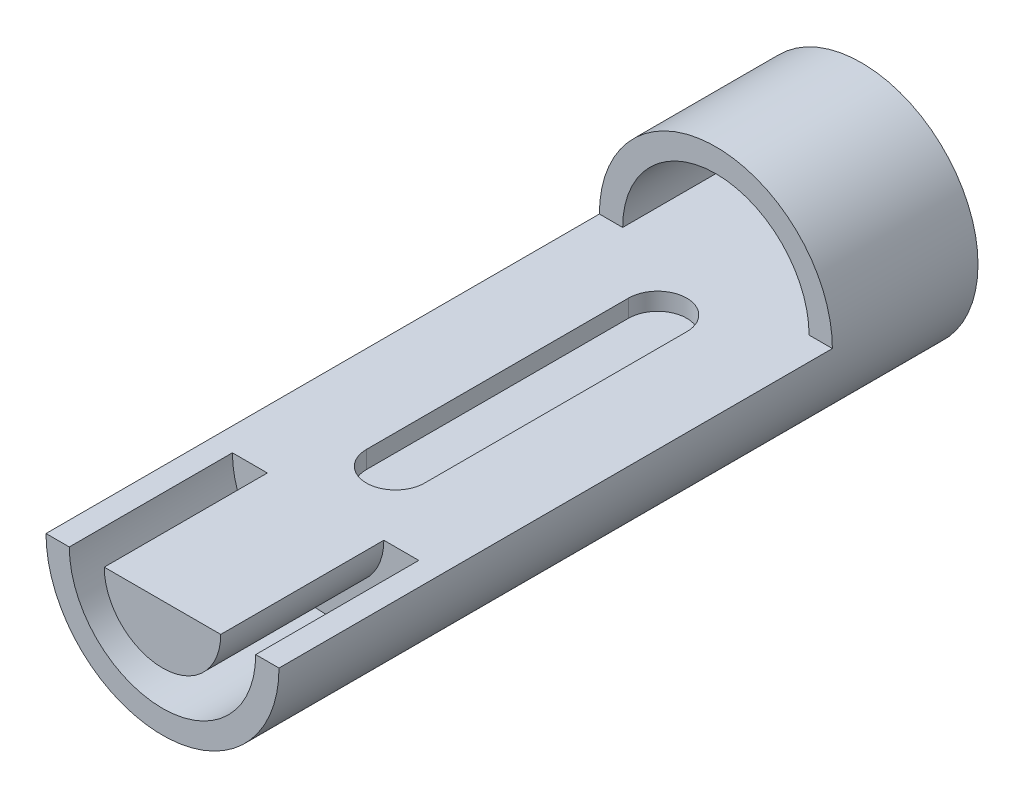
SolidWorks part; units mm, degrees
material "Copper"
ref_plane "Front Plane" through (0, 0, 0) normal (0, 0, 1) x (1, 0, 0)
ref_plane "Top Plane" through (0, 0, 0) normal (0, 1, 0) x (1, 0, 0)
ref_plane "Right Plane" through (0, 0, 0) normal (1, 0, 0) x (0, 0, -1)
sketch "Sketch2" plane through (0, 0, 0) normal (0, 0, 1) x (1, 0, 0)
  circle A0 centre (0, 0) radius 20
  dimension "D1" = 40
extrude "Boss-Extrude2" add sketch "Sketch2" along normal blind 120
extrude "Boss-Extrude3" add sketch "Sketch2<3>" along normal blind 120
sketch "Sketch2<3>" plane through (0, 0, 0) normal (0, 0, 1) x (1, 0, 0) same geometry as "Sketch2"
sketch "Sketch4" plane through (0, 0, 120) normal (0, 0, 1) x (1, 0, 0)
  line L0 (-20, 0) -> (20, 0)
  circle A3 centre (0, 0) radius 20 construction
  arc A4 (20, 0) -> (-20, 0) centre (0, 0) ccw
  point P2 (15.4919, 4)
  point P6 (15.4919, 4)
  point P8 (-20, 0)
  point P9 (20, 0)
  point P12 (15.4919, 4)
extrude "Cut-Extrude1" cut sketch "Sketch4" against normal blind 95
sketch "Sketch5" plane through (0, 0, 25) normal (0, 0, 1) x (1, 0, 0)
  line L0 (-20, 0) -> (20, 0) construction
  line L1 (-20, 0) -> (20, 0)
  arc A0 (16, 0) -> (-16, 0) centre (0, 0) ccw
  arc A1 (20, 0) -> (-20, 0) centre (0, 0) ccw construction
  arc A3 (20, 0) -> (-20, 0) centre (0, 0) ccw
  dimension "D1" = 32
extrude "Cut-Extrude2" cut sketch "Sketch5" against normal through all contours L1 A0 region at (0, 6.7906, 25)
sketch "Sketch6" plane through (0, 0, 120) normal (0, 0, 1) x (1, 0, 0)
  line L0 (-20, 0) -> (20, 0) construction
  line L1 (-20, 0) -> (20, 0)
  arc A0 (-16, 0) -> (16, 0) centre (0, 0) ccw
  arc A1 (-10, 0) -> (10, 0) centre (0, 0) ccw
  arc A2 (-20, 0) -> (20, 0) centre (0, 0) ccw construction
  arc A3 (-20, 0) -> (20, 0) centre (0, 0) ccw
extrude "Cut-Extrude3" cut sketch "Sketch6" against normal blind 28 contours A1 L1 A0 region at (-13, -0.3578, 120)
sketch "Sketch7" plane through (0, 0, 0) normal (0, 1, 0) x (1, 0, 0)
  line L0 (0, 9.2922) -> (0, -139.7751)
  line L1 (0, -35) -> (0, -80) construction
  line L2 (5, -35) -> (5, -80)
  line L3 (-5, -35) -> (-5, -80)
  arc A0 (5, -35) -> (-5, -35) centre (0, -35) ccw
  arc A1 (-5, -80) -> (5, -80) centre (0, -80) ccw
  point P5 (0, -57.5)
  dimension "D1" = 5
  dimension "D2" = 45
  dimension "D3" = 40
extrude "Cut-Extrude4" cut sketch "Sketch7" against normal blind 3 contours L3 A1 L0 A0 | L0 A1 L2 A0 region at (2.4438, 0, 57.5) region at (-2.4438, 0, 57.5)
